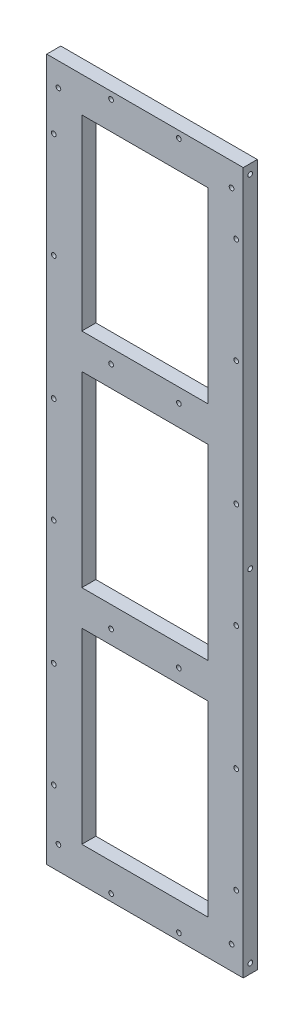
SolidWorks part; units mm, degrees
material "Alumina"
ref_plane "Front Plane" through (0, 0, 0) normal (0, 0, 1) x (1, 0, 0)
ref_plane "Top Plane" through (0, 0, 0) normal (0, 1, 0) x (1, 0, 0)
ref_plane "Right Plane" through (0, 0, 0) normal (1, 0, 0) x (0, 0, -1)
sketch "Sketch1" plane through (0, 0, 0) normal (0, 0, 1) x (1, 0, 0)
  line L0 (27, 135) -> (27, 55)
  line L9 (-42, -150) -> (42, -150)
  line L10 (-42, -150) -> (-42, 150)
  line L11 (-42, 150) -> (42, 150)
  line L12 (42, -150) -> (42, 150)
  line L13 (0, 0) -> (0, 40) construction
  line L15 (-27, -135) -> (27, -135)
  line L16 (-27, -135) -> (-27, -55)
  line L17 (-27, 135) -> (27, 135)
  line L21 (-27, 55) -> (27, 55)
  line L23 (-27, 40) -> (27, 40)
  line L25 (-27, -40) -> (27, -40)
  line L27 (-27, -55) -> (27, -55)
  line L33 (27, 40) -> (27, -40)
  line L34 (-27, 55) -> (-27, 135)
  line L35 (-27, -40) -> (-27, 40)
  line L36 (27, -55) -> (27, -135)
  dimension "D1" = 84
  dimension "D2" = 300
  dimension "D3" = 54
  dimension "D4" = 270
  dimension "D5" = 15
  dimension "D6" = 80
  dimension "D7" = 15
  dimension "D8" = 80
  dimension "D9" = 15
  dimension "D10" = 15
  dimension "D11" = 80
  dimension "D12" = 40
  dimension "D13" = 15
extrude "Boss-Extrude1" add sketch "Sketch1" along normal blind 6
sketch "Sketch2" plane through (42, 0, 0) normal (1, 0, 0) x (0, 0, -1)
  line L0 (-6, 150) -> (0, 150) construction
  line L1 (-6, -150) -> (-6, 150) construction
  line L3 (-3, 146) -> (-3, 0) construction
  circle A0 centre (-3, 146) radius 1
  circle A4 centre (-3, 0) radius 1
  circle A5 centre (-3, -146) radius 1
  circle A6 centre (-3, -292) radius 1
  dimension "D1" = 4
  dimension "D3" = 2
  dimension "D4" = 3
  dimension "D2" = 4
  dimension "D5" = 146
extrude "Cut-Extrude1" cut sketch "Sketch2" against normal blind 10
mirror "Mirror1" about plane through (0, 0, 0) normal (1, 0, 0) of "Cut-Extrude1"
sketch "Sketch4" plane through (0, 0, 6) normal (0, 0, 1) x (1, 0, 0)
  line L0 (-42, -150) -> (-42, 150) construction
  line L1 (42, -150) -> (42, 150) construction
  line L2 (-42, 150) -> (42, 150) construction
  line L3 (42, 150) -> (-42, 150) construction
  line L4 (-14.5, 147) -> (-14.5, 49) construction
  line L6 (-39, 122) -> (39, 122) construction
  line L7 (-39, 122) -> (-39, 77) construction
  line L8 (-39, 122) -> (-39, 24) construction
  circle A0 centre (-14.5, 147) radius 1
  circle A1 centre (14.5, 147) radius 1
  circle A8 centre (-39, 122) radius 1
  circle A20 centre (-14.5, 49) radius 1
  circle A21 centre (14.5, 49) radius 1
  circle A22 centre (-14.5, -49) radius 1
  circle A23 centre (14.5, -49) radius 1
  circle A24 centre (-14.5, -147) radius 1
  circle A25 centre (14.5, -147) radius 1
  circle A29 centre (39, 122) radius 1
  circle A30 centre (39, 77) radius 1
  circle A31 centre (-39, 77) radius 1
  circle A32 centre (-39, 24) radius 1
  circle A33 centre (39, 24) radius 1
  circle A34 centre (39, -21) radius 1
  circle A35 centre (-39, -21) radius 1
  circle A36 centre (-39, -74) radius 1
  circle A37 centre (39, -74) radius 1
  circle A38 centre (39, -119) radius 1
  circle A39 centre (-39, -119) radius 1
  dimension "D1" = 27.5
  dimension "D4" = 78
  dimension "D7" = 45
  dimension "D10" = 2
  dimension "D11" = 2
  dimension "D3" = 3
  dimension "D6" = 3
  dimension "D14" = 2
  dimension "D15" = 2
  dimension "D16" = 98
  dimension "D2" = 27.5
  dimension "D5" = 28
  dimension "D9" = 3
  dimension "D13" = 98
  dimension "D12" = 4
  dimension "D8" = 2
extrude "Cut-Extrude3" cut sketch "Sketch4" against normal blind 10
sketch "Sketch5" plane through (0, 150, 0) normal (0, 1, 0) x (1, 0, 0)
  line L0 (42, -6) -> (-42, -6) construction
  circle A0 centre (0, -3) radius 1
  point P5 (0, -6)
  dimension "D1" = 3
  dimension "D2" = 2
sketch "Sketch6" plane through (0, 0, 6) normal (0, 0, 1) x (1, 0, 0)
  line L0 (-42, 150) -> (-42, -150) construction
  line L1 (42, 150) -> (-42, 150) construction
  circle A0 centre (-37, 140) radius 1
  dimension "D1" = 2
  dimension "D2" = 5
  dimension "D3" = 10
extrude "Cut-Extrude5" cut sketch "Sketch6" against normal blind 10
pattern_linear "LPattern1" count 2 spacing 74 along (1, 0, 0) count 2 spacing 280 along (0, -1, 0) of "Cut-Extrude5"
